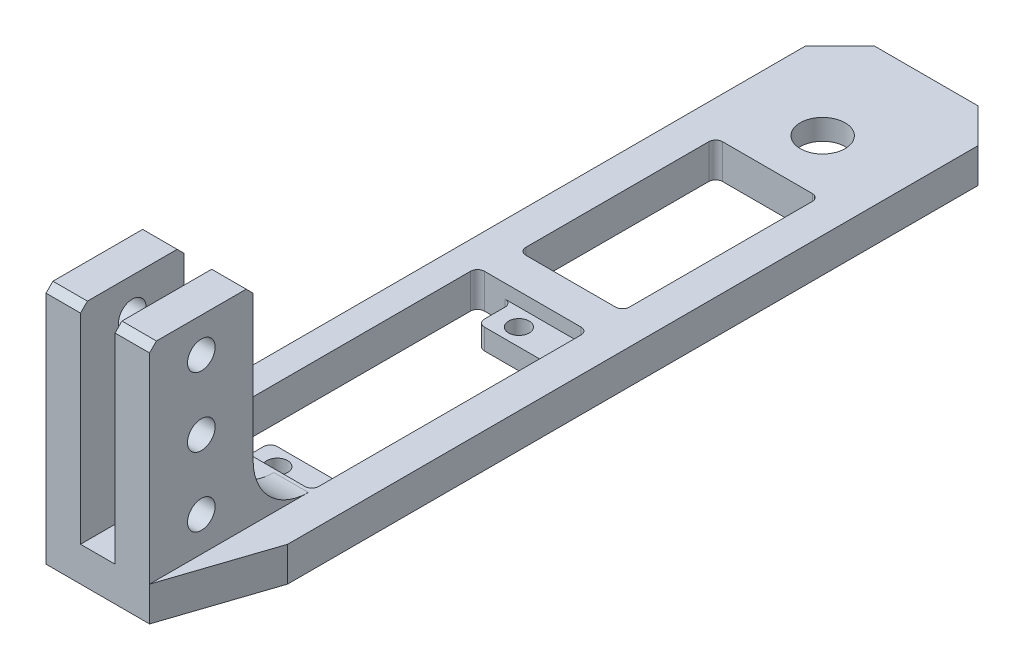
SolidWorks part; units mm, degrees
material "PLA"
ref_plane "Front" through (0, 0, 0) normal (0, 0, 1) x (1, 0, 0)
ref_plane "Top" through (0, 0, 0) normal (0, 1, 0) x (1, 0, 0)
ref_plane "Right" through (0, 0, 0) normal (1, 0, 0) x (0, 0, -1)
sketch "Sketch1" plane through (0, 0, 0) normal (0, 1, 0) x (1, 0, 0)
  line L1 (-12.5, -60) -> (12.5, -60)
  line L2 (-12.5, -60) -> (-12.5, 60)
  line L3 (-12.5, 60) -> (12.5, 60)
  line L4 (12.5, -60) -> (12.5, 60)
  line L5 (-12.5, -60) -> (12.5, 60) construction
  line L6 (-12.5, 60) -> (12.5, -60) construction
  point P0 (0, 0)
  dimension "D1" = 120
  dimension "D2" = 25
extrude "Boss-Extrude1" add sketch "Sketch1" along normal blind 5
sketch "Sketch2" plane through (0, 5, 0) normal (0, 1, 0) x (1, 0, 0)
  line L0 (-12.5, -60) -> (12.5, -60) construction
  line L1 (-7.5, -60) -> (7.5, -60)
  line L2 (-7.5, -60) -> (-7.5, -45)
  line L3 (-7.5, -45) -> (7.5, -45)
  line L4 (7.5, -60) -> (7.5, -45)
  line L5 (0, 0) -> (0, -7.7795) construction
  line L7 (-2.5, -45) -> (2.5, -45)
  line L8 (-2.5, -45) -> (-2.5, -60)
  line L9 (-2.5, -60) -> (2.5, -60)
  line L10 (2.5, -45) -> (2.5, -60)
  line M9 (-12.5, -60) -> (12.5, -60)
  dimension "D1" = 15
  dimension "D2" = 15
  dimension "D3" = 5
extrude "Boss-Extrude2" add sketch "Sketch2" along normal blind 30 contours L8 L3 L2 M9 | L3 L10 L4 M9 region at (-5, 5, 52.5) region at (5, 5, 52.5)
chamfer "Chamfer1" distance 5 distance2 15 1 edges at (12.5, 2.5, 60) first distance on face at (0, 14.1667, 60)
chamfer "Chamfer2" distance 15 distance2 5 1 edges at (-12.5, 2.5, 60) first distance on face at (-12.5, 2.5, 0)
chamfer "Chamfer3" distance 1 angle 45 4 edges at (5, 35, 60) (-5, 35, 60) (-5, 35, 45) (5, 35, 45)
chamfer "Chamfer4" distance 5 angle 45 2 edges at (-12.5, 2.5, -60) (12.5, 2.5, -60)
sketch "Sketch5" plane through (0, 5, 0) normal (0, 1, 0) x (1, 0, 0)
  line L0 (-2.5, -60) -> (2.5, -60) construction
  line L1 (7.5, 60) -> (-7.5, 60) construction
  circle A0 centre (0, -7.5) radius 5 construction
  circle A1 centre (0, 45) radius 5 construction
  dimension "D2" = 10
  dimension "D4" = 10
  dimension "D1" = 52.5
  dimension "D3" = 15
sketch "Sketch3" plane through (0, 5, 0) normal (0, 1, 0) x (1, 0, 0)
  line L0 (0, 0) -> (0, 25.0391) construction
  line L1 (-8.5, -36.5) -> (7.5, -36.5)
  line L2 (-8.5, -36.5) -> (-8.5, 3.5)
  line L3 (-8.5, 3.5) -> (7.5, 3.5)
  line L4 (7.5, -36.5) -> (7.5, 3.5)
  line L5 (-8.5, -36.5) -> (7.5, 3.5) construction
  line L6 (-8.5, 3.5) -> (7.5, -36.5) construction
  line L7 (-0.5, -16.5) -> (-22.7755, -16.5) construction
  line L8 (-3.5, 3.5) -> (7.5, 3.5)
  line L9 (-3.5, 3.5) -> (-3.5, -1.5)
  line L10 (-3.5, -1.5) -> (7.5, -1.5)
  line L11 (7.5, 3.5) -> (7.5, -1.5)
  line L12 (-3.5, -36.5) -> (7.5, -36.5)
  line L13 (-3.5, -36.5) -> (-3.5, -31.5)
  line L14 (-3.5, -31.5) -> (7.5, -31.5)
  line L15 (7.5, -36.5) -> (7.5, -31.5)
  line L16 (12.5, -45) -> (12.5, 55) construction
  point P0 (-0.5, -16.5)
  dimension "D1" = 16
  dimension "D2" = 40
  dimension "D3" = 11
  dimension "D4" = 5
  dimension "D5" = 11
  dimension "D7" = 5
extrude "Cut-Extrude1" cut sketch "Sketch3" against normal through all contours L15 L1 L4 L3 L11 L10 L9 L2 L13 L14 region at (-1.0189, 5, 16.5)
extrude "Cut-Extrude2" cut sketch "Sketch3<3>" against normal blind 2 contours L11 L3 L9 L10 | L1 L15 L14 L13 region at (2, 5, 34) region at (2, 5, -1)
sketch "Sketch3<3>" plane through (0, 5, 0) normal (0, 1, 0) x (1, 0, 0) same geometry as "Sketch3"
fillet "Fillet1" radius 1 8 edges at (7.5, 4, 36.5) (-3.5, 1.5, 31.5) (-3.5, 1.5, 36.5) (-8.5, 2.5, 36.5) (-3.5, 1.5, 1.5) (-3.5, 1.5, -3.5) (7.5, 4, -3.5) (-8.5, 2.5, -3.5)
sketch "Sketch4" plane through (0, 3, 0) normal (0, 1, 0) x (1, 0, 0)
  line L0 (0, 3.5) -> (0, -28.1892) construction
  line L1 (-4.5, 3.5) -> (6.5, 3.5) construction
  circle A0 centre (0, 1) radius 1.5
  circle A1 centre (0, -34) radius 1.5
  dimension "D2" = 3
  dimension "D1" = 35
  dimension "D3" = 2.5
extrude "Cut-Extrude3" cut sketch "Sketch4" against normal through all
fillet "Fillet2" radius 8 2 edges at (-5, 5, 45) (5, 5, 45)
sketch "Sketch6" plane through (0, 5, 0) normal (0, 1, 0) x (1, 0, 0)
  circle A0 centre (0, 45) radius 3.25
  dimension "D1" = 6.5
extrude "Cut-Extrude5" cut sketch "Sketch6" against normal through all
sketch "Sketch7" plane through (0, 0, 0) normal (0, -1, 0) x (1, 0, 0)
  line L0 (-6.6849, -39.75) -> (6.6849, -39.75)
  line L1 (-6.6849, -50.25) -> (6.6849, -50.25)
  line L2 (0, -45) -> (-19.1578, -45) construction
  circle A0 centre (0, -45) radius 8.5 construction
  arc A1 (-6.6849, -39.75) -> (-6.6849, -50.25) centre (0, -45) ccw
  arc A2 (6.6849, -39.75) -> (6.6849, -50.25) centre (0, -45) cw
  dimension "D1" = 17
  dimension "D2" = 10.5
extrude "Cut-Extrude6" cut sketch "Sketch7" against normal blind 2
sketch "Sketch8" plane through (0, 2, 0) normal (0, -1, 0) x (1, 0, 0)
  line L0 (0, -45) -> (-2.0583, -45) construction
  line L1 (-8.5, -43.75) -> (-6.5, -43.75)
  line L2 (-8.5, -43.75) -> (-8.5, -46.25)
  line L3 (-8.5, -46.25) -> (-6.5, -46.25)
  line L4 (-6.5, -43.75) -> (-6.5, -46.25)
  arc A0 (-6.6849, -39.75) -> (-6.6849, -50.25) centre (0, -45) ccw construction
  dimension "D1" = 2.5
  dimension "D2" = 2
extrude "Cut-Extrude7" cut sketch "Sketch8" against normal blind 1
sketch "Sketch9" plane through (7.5, 0, 0) normal (1, 0, 0) x (0, 0, -1)
  line L1 (-52.5, 35) -> (-52.5, 41.8125) construction
  line L2 (-59, 35) -> (-46, 35) construction
  circle A0 centre (-52.5, 30) radius 2
  circle A1 centre (-52.5, 20) radius 2
  circle A2 centre (-52.5, 10) radius 2
  dimension "D3" = 4
  dimension "D1" = 10
  dimension "D2" = 10
  dimension "D4" = 5
extrude "Cut-Extrude8" cut sketch "Sketch9" against normal through all
sketch "Sketch10" plane through (0, 5, 0) normal (0, 1, 0) x (1, 0, 0)
  line L0 (-7.5, 3.5) -> (6.5, 3.5) construction
  line L1 (-7.5, 37) -> (7.5, 37)
  line L2 (-7.5, 37) -> (-7.5, 8.5)
  line L3 (-7.5, 8.5) -> (7.5, 8.5)
  line L4 (7.5, 37) -> (7.5, 8.5)
  line L7 (-12.5, 55) -> (-12.5, -45) construction
  line L8 (12.5, -45) -> (12.5, 55) construction
  dimension "D1" = 8
  dimension "D2" = 5
  dimension "D3" = 5
  dimension "D4" = 5
extrude "Cut-Extrude9" cut sketch "Sketch10" against normal through all
fillet "Fillet3" radius 1 4 edges at (-7.5, 2.5, -8.5) (7.5, 2.5, -8.5) (7.5, 2.5, -37) (-7.5, 2.5, -37)
